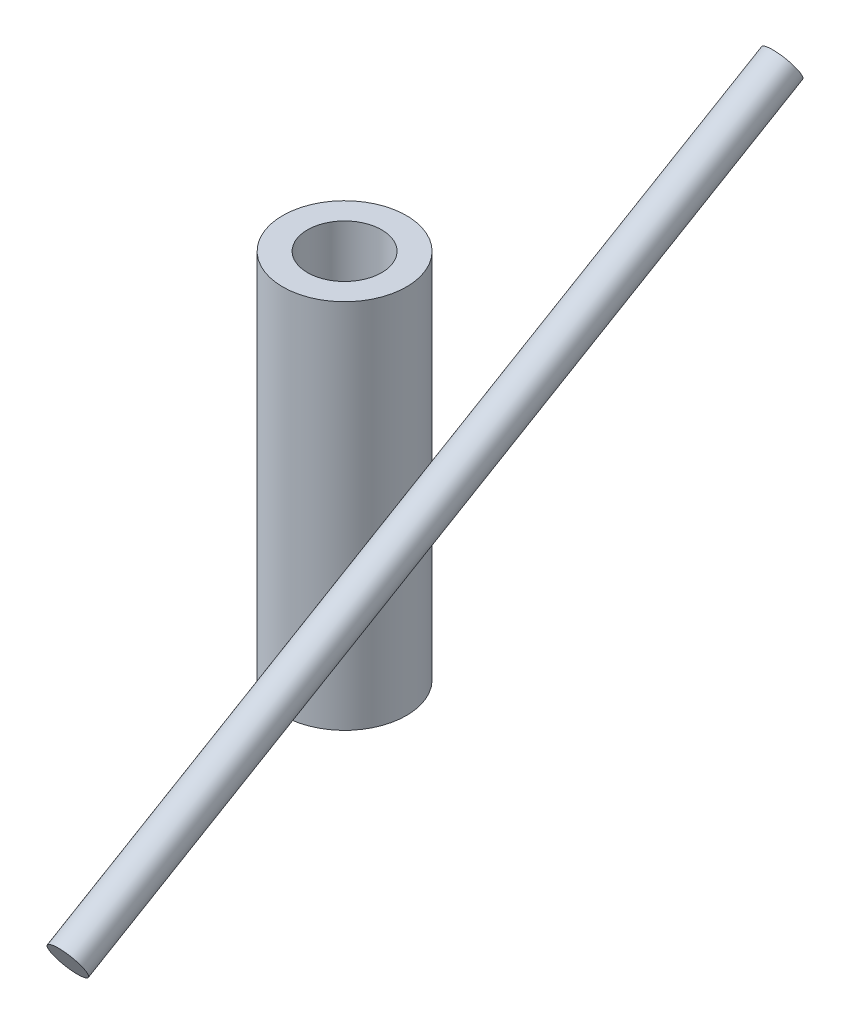
SolidWorks part; units mm, degrees
ref_plane "Спереди" through (0, 0, 0) normal (0, 0, 1) x (1, 0, 0)
ref_plane "Сверху" through (0, 0, 0) normal (0, 1, 0) x (1, 0, 0)
ref_plane "Справа" through (0, 0, 0) normal (1, 0, 0) x (0, 0, -1)
sketch "Эскиз1" plane through (0, 0, 0) normal (0, 1, 0) x (1, 0, 0)
  circle A0 centre (0, 0) radius 5
  circle A1 centre (0, 0) radius 3
  dimension "D1" = 6
  dimension "D2" = 10
extrude "Бобышка-Вытянуть1" add sketch "Эскиз1" along normal blind 15 and the other way blind 15
ref_plane "Плоскость1" through (5, 0, 0) normal (1, 0, 0) x (0, 0, -1)
sketch "Эскиз2" plane through (5, 0, 0) normal (1, 0, 0) x (0, 0, -1)
  line L0 (-28.8661, -17) -> (28.8661, 17)
  line L1 (5, 15) -> (-5, 15) construction
  point P4 (0, 0)
  dimension "D1" = 67
  dimension "D2" = 2
ref_plane "Плоскость2" through (5, -17, 28.8661) normal (0, 0.5075, -0.8617) x (-1, 0, 0)
sketch "Эскиз3" plane through (5, -17, 28.8661) normal (0, 0.5075, -0.8617) x (-1, 0, 0)
  circle A0 centre (-1.5, 0) radius 1.5
  dimension "D1" = 3
sweep "По траектории1" add profiles "Эскиз3" path "Эскиз2"
sketch "Эскиз4" plane through (0, 0, 0) normal (1, 0, 0) x (0, 0, -1)
  circle A0 centre (0, 0) radius 2
  dimension "D1" = 4
extrude "Вырез-Вытянуть1" cut sketch "Эскиз4" against normal blind 15
